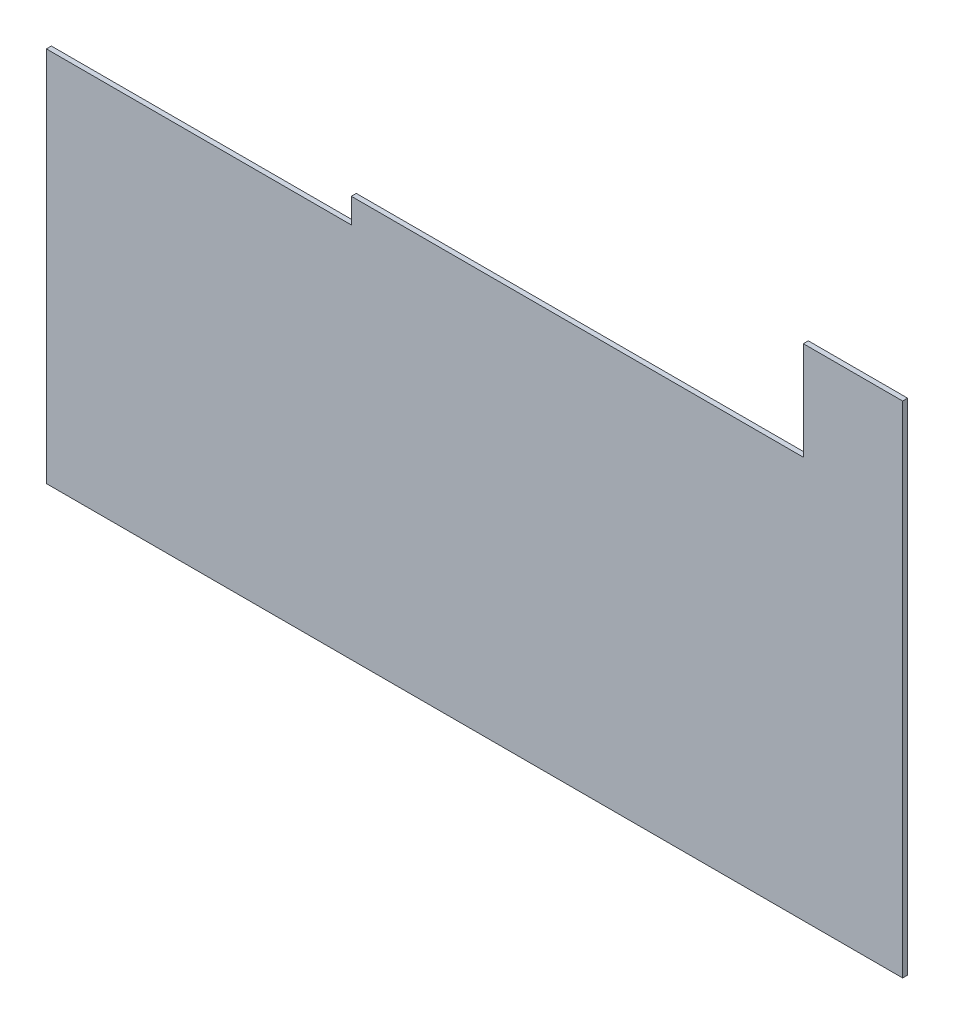
SolidWorks part; units mm, degrees
ref_plane "Ön Düzlem" through (0, 0, 0) normal (0, 0, 1) x (1, 0, 0)
ref_plane "Üst Düzlem" through (0, 0, 0) normal (0, 1, 0) x (1, 0, 0)
ref_plane "Sağ Düzlem" through (0, 0, 0) normal (1, 0, 0) x (0, 0, -1)
sketch "Çizim1" plane through (0, 0, 0) normal (0, 0, 1) x (1, 0, 0)
  line L0 (0, 0) -> (0, 1895)
  line L1 (2935, 2020) -> (4900, 2020)
  line L2 (4900, 2020) -> (4900, 2515)
  line L3 (4900, 2515) -> (6002, 2515)
  line L4 (6002, 2515) -> (6002, 0)
  line L5 (6002, 0) -> (0, 0)
  line L8 (2935, 2020) -> (2935, 1895)
  line L9 (2935, 1895) -> (0, 1895)
  dimension "D1" = 125
  dimension "D2" = 620
  dimension "D3" = 2935
  dimension "D4" = 495
  dimension "D5" = 1102
  dimension "D6" = 2020
  dimension "D7" = 2515
  dimension "D8" = 6002
  dimension "D9" = 1965
  dimension "D10" = 4900
base flange "Taban-Flanş1" sketch "Çizim1" thickness 25 reverse thickness direction no parameters "D1"=8
sketch "Çizim6" plane through (0, 0, -25) normal (0, 0, -1) x (-1, 0, 0)
  line L1 (-4900, 2515) -> (0, 2515)
  line L2 (-4900, 2515) -> (-4900, 2020)
  line L3 (-4900, 2020) -> (0, 2020)
  line L4 (0, 2515) -> (0, 2020)
  line L5 (-2935, 1895) -> (0, 1895) construction
  line L6 (-2935, 2020) -> (-2935, 1895) construction
  dimension "D1" = 4900
  dimension "D2" = 495
  dimension "D3" = 125
  dimension "D4" = 2935
sketch "Çizim7" plane through (0, 0, 0) normal (0, 0, 1) x (1, 0, 0)
  line L0 (0, 0) -> (6002, 0) construction
  line L1 (0, 1895) -> (1400, 1895)
  line L2 (0, 1895) -> (0, 0)
  line L3 (0, 0) -> (1400, 0)
  line L4 (1400, 1895) -> (1400, 0)
  line L5 (2935, 2020) -> (2935, 1895) construction
  line L6 (4900, 2020) -> (2935, 2020) construction
  line L7 (4900, 2515) -> (5210, 2515)
  line L8 (4900, 2515) -> (4900, 2020)
  line L9 (4900, 2020) -> (5210, 2020)
  line L10 (5210, 2515) -> (5210, 2020)
  line L11 (6002, 0) -> (6002, 2515) construction
  dimension "D1" = 1535
  dimension "D2" = 1400
  dimension "D3" = 1895
  dimension "D4" = 2275
  dimension "D5" = 310
  dimension "D6" = 495
  dimension "D7" = 792
extrude "Kes-Ekstrüzyon1" cut sketch "Çizim7" against normal through all both and the other way through all
sketch "Çizim8" plane through (0, 0, 0) normal (0, 0, 1) x (1, 0, 0)
  line L0 (1400, 0) -> (6002, 0) construction
  line L1 (6002, 2515) -> (5710, 2515)
  line L2 (6002, 2515) -> (6002, 0)
  line L3 (6002, 0) -> (5710, 0)
  line L4 (5710, 2515) -> (5710, 0)
  line L5 (5210, 2515) -> (5210, 2020) construction
  dimension "D1" = 500
  dimension "D2" = 2515
  dimension "D3" = 292
extrude "Kes-Ekstrüzyon2" cut sketch "Çizim8" against normal through all both and the other way through all
sketch "Çizim10" plane through (0, 0, 0) normal (0, 0, 1) x (1, 0, 0)
  line L0 (5210, 2020) -> (2935, 2020) construction
  line L1 (4395, 2020) -> (1400, 2020)
  line L2 (4395, 2020) -> (4395, 1630)
  line L3 (4395, 1630) -> (1400, 1630)
  line L4 (1400, 2020) -> (1400, 1630)
  line L5 (1400, 1895) -> (1400, 0) construction
  line L6 (1400, 0) -> (5710, 0) construction
  line L7 (2935, 2020) -> (2935, 1895) construction
  line L8 (2935, 1895) -> (1400, 1895) construction
  dimension "D1" = 2995
  dimension "D2" = 1630
  dimension "D3" = 1460
  dimension "D4" = 265
sketch "Büküm-Çizgileri1" [suppressed] plane through (0, 0, 0) normal (0, 1, 0) x (1, 0, 0)
sketch "Sınırlandırma-Kutusu1" [suppressed] plane through (0, 0, 0) normal (0, 1, 0) x (1, 0, 0)
sheet metal parameters "Sac-Levha1" thickness 25 parameters "D1"=8
flat pattern "Düz-Çoğaltma1" [suppressed]
sketch "Büküm-Çizgileri2" plane through (0, 0, 0) normal (0, 1, 0) x (1, 0, 0)
sketch3d "Sınırlandırma-Kutusu2" [suppressed]
  line L0 (0, 0, 0) -> (6002, 0, 0) construction
  line L1 (0, 2515, 0) -> (6002, 2515, 0) construction
  line L2 (0, 0, 0) -> (0, 2515, 0) construction
  line L3 (6002, 0, 0) -> (6002, 2515, 0) construction
sketch "Çizim6-1" [suppressed] plane through (0, 0, -25) normal (0, 0, -1) x (-1, 0, 0)
  line L1 (-4900, 2515) -> (0, 2515)
  line L2 (-4900, 2515) -> (-4900, 2020)
  line L3 (-4900, 2020) -> (0, 2020)
  line L4 (0, 2515) -> (0, 2020)
  line L5 (-2935, 1895) -> (0, 1895) construction
  line L6 (-2935, 2020) -> (-2935, 1895) construction
  dimension "D1" = 4900
  dimension "D2" = 495
  dimension "D3" = 125
  dimension "D4" = 2935
sheet metal parameters "Sac-Levha2" thickness 25 parameters "D1"=8
flat pattern "Düz-Çoğaltma1" [suppressed]
sketch "Büküm-Çizgileri2" plane through (0, 0, 0) normal (0, 1, 0) x (1, 0, 0)
sketch3d "Sınırlandırma-Kutusu2" [suppressed]
  line L0 (1400, 0, 0) -> (6002, 0, 0) construction
  line L1 (1400, 2515, 0) -> (6002, 2515, 0) construction
  line L2 (1400, 0, 0) -> (1400, 2515, 0) construction
  line L3 (6002, 0, 0) -> (6002, 2515, 0) construction
sketch "Çizim6-1" [suppressed] plane through (0, 0, -25) normal (0, 0, -1) x (-1, 0, 0)
  line L1 (-4900, 2515) -> (0, 2515)
  line L2 (-4900, 2515) -> (-4900, 2020)
  line L3 (-4900, 2020) -> (0, 2020)
  line L4 (0, 2515) -> (0, 2020)
  line L5 (-2935, 1895) -> (-1400, 1895) construction
  line L6 (-2935, 2020) -> (-2935, 1895) construction
  dimension "D1" = 4900
  dimension "D2" = 495
  dimension "D3" = 125
  dimension "D4" = 2935
sketch "Çizim6-2" [suppressed] plane through (0, 0, -25) normal (0, 0, -1) x (-1, 0, 0)
  line L1 (-4900, 2515) -> (0, 2515)
  line L2 (-4900, 2515) -> (-4900, 2020)
  line L3 (-4900, 2020) -> (0, 2020)
  line L4 (0, 2515) -> (0, 2020)
  line L5 (-2935, 1895) -> (-1400, 1895) construction
  line L6 (-2935, 2020) -> (-2935, 1895) construction
  dimension "D1" = 4900
  dimension "D2" = 495
  dimension "D3" = 125
  dimension "D4" = 2935
sketch "Çizim6-3" [suppressed] plane through (0, 0, -25) normal (0, 0, -1) x (-1, 0, 0)
  line L1 (-4900, 2515) -> (0, 2515)
  line L2 (-4900, 2515) -> (-4900, 2020)
  line L3 (-4900, 2020) -> (0, 2020)
  line L4 (0, 2515) -> (0, 2020)
  line L5 (-2935, 1895) -> (-1400, 1895) construction
  line L6 (-2935, 2020) -> (-2935, 1895) construction
  dimension "D1" = 4900
  dimension "D2" = 495
  dimension "D3" = 125
  dimension "D4" = 2935
sheet metal parameters "Sac-Levha3" thickness 25 parameters "D1"=8
flat pattern "Düz-Çoğaltma1" [suppressed]
sketch "Büküm-Çizgileri2" plane through (0, 0, 0) normal (0, 1, 0) x (1, 0, 0)
sketch3d "Sınırlandırma-Kutusu2" [suppressed]
  line L0 (1400, 0, 0) -> (5710, 0, 0) construction
  line L1 (1400, 2515, 0) -> (5710, 2515, 0) construction
  line L2 (1400, 0, 0) -> (1400, 2515, 0) construction
  line L3 (5710, 0, 0) -> (5710, 2515, 0) construction
sketch "Çizim6-1" [suppressed] plane through (0, 0, -25) normal (0, 0, -1) x (-1, 0, 0)
  line L1 (-4900, 2515) -> (0, 2515)
  line L2 (-4900, 2515) -> (-4900, 2020)
  line L3 (-4900, 2020) -> (0, 2020)
  line L4 (0, 2515) -> (0, 2020)
  line L5 (-2935, 1895) -> (-1400, 1895) construction
  line L6 (-2935, 2020) -> (-2935, 1895) construction
  dimension "D1" = 4900
  dimension "D2" = 495
  dimension "D3" = 125
  dimension "D4" = 2935
sketch "Çizim6-2" [suppressed] plane through (0, 0, -25) normal (0, 0, -1) x (-1, 0, 0)
  line L1 (-4900, 2515) -> (0, 2515)
  line L2 (-4900, 2515) -> (-4900, 2020)
  line L3 (-4900, 2020) -> (0, 2020)
  line L4 (0, 2515) -> (0, 2020)
  line L5 (-2935, 1895) -> (-1400, 1895)
  line L6 (-2935, 2020) -> (-2935, 1895)
  dimension "D1" = 4900
  dimension "D2" = 495
  dimension "D3" = 125
  dimension "D4" = 2935
sketch "Çizim6-3" [suppressed] plane through (0, 0, -25) normal (0, 0, -1) x (-1, 0, 0)
  line L1 (-4900, 2515) -> (0, 2515)
  line L2 (-4900, 2515) -> (-4900, 2020)
  line L3 (-4900, 2020) -> (0, 2020)
  line L4 (0, 2515) -> (0, 2020)
  line L5 (-2935, 1895) -> (-1400, 1895)
  line L6 (-2935, 2020) -> (-2935, 1895)
  dimension "D1" = 4900
  dimension "D2" = 495
  dimension "D3" = 125
  dimension "D4" = 2935
sketch "Çizim6-4" [suppressed] plane through (0, 0, -25) normal (0, 0, -1) x (-1, 0, 0)
  line L1 (-4900, 2515) -> (0, 2515)
  line L2 (-4900, 2515) -> (-4900, 2020)
  line L3 (-4900, 2020) -> (0, 2020)
  line L4 (0, 2515) -> (0, 2020)
  line L5 (-2935, 1895) -> (-1400, 1895) construction
  line L6 (-2935, 2020) -> (-2935, 1895) construction
  dimension "D1" = 4900
  dimension "D2" = 495
  dimension "D3" = 125
  dimension "D4" = 2935
sketch "Çizim6-5" [suppressed] plane through (0, 0, -25) normal (0, 0, -1) x (-1, 0, 0)
  line L1 (-4900, 2515) -> (0, 2515)
  line L2 (-4900, 2515) -> (-4900, 2020)
  line L3 (-4900, 2020) -> (0, 2020)
  line L4 (0, 2515) -> (0, 2020)
  line L5 (-2935, 1895) -> (-1400, 1895) construction
  line L6 (-2935, 2020) -> (-2935, 1895) construction
  dimension "D1" = 4900
  dimension "D2" = 495
  dimension "D3" = 125
  dimension "D4" = 2935
